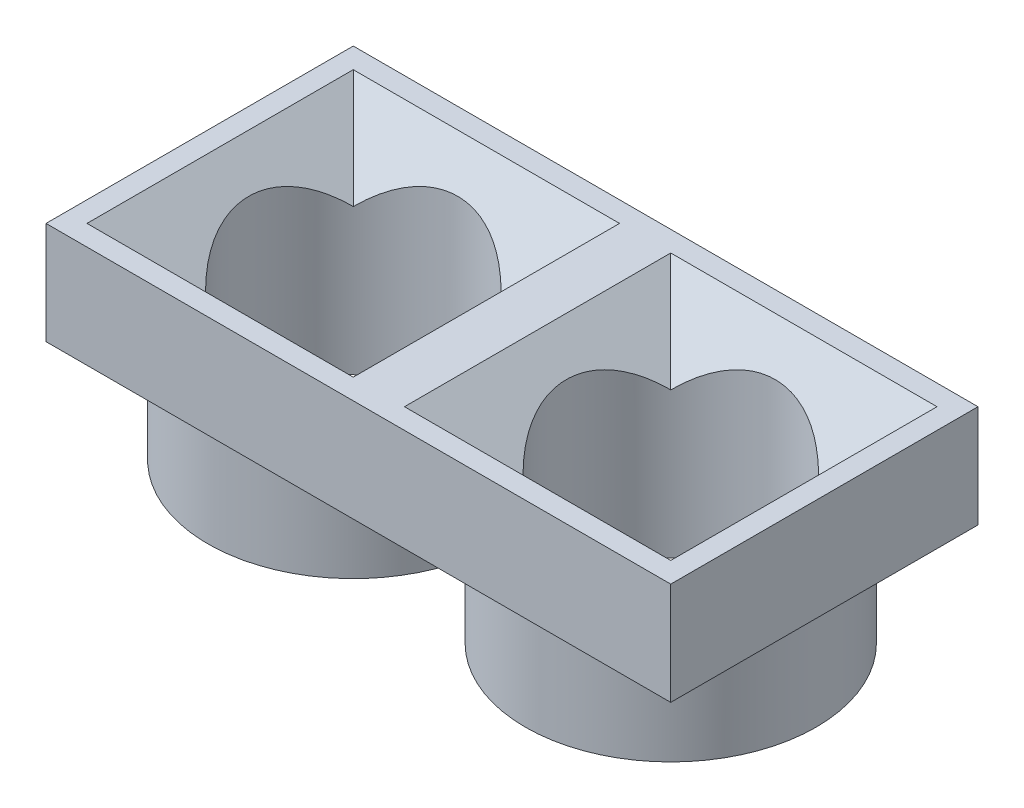
SolidWorks part; units mm, degrees
ref_plane "Front Plane" through (0, 0, 0) normal (0, 0, 1) x (1, 0, 0)
ref_plane "Top Plane" through (0, 0, 0) normal (0, 1, 0) x (1, 0, 0)
ref_plane "Right Plane" through (0, 0, 0) normal (1, 0, 0) x (0, 0, -1)
sketch "Sketch1" plane through (0, 0, 0) normal (0, 1, 0) x (1, 0, 0)
  line L1 (-15.25, 7.5) -> (15.25, 7.5)
  line L2 (-15.25, 7.5) -> (-15.25, -7.5)
  line L3 (-15.25, -7.5) -> (15.25, -7.5)
  line L4 (15.25, 7.5) -> (15.25, -7.5)
  line L5 (-15.25, 7.5) -> (15.25, -7.5) construction
  line L6 (-15.25, -7.5) -> (15.25, 7.5) construction
  point P0 (0, 0)
  dimension "D1" = 15
  dimension "D2" = 30.5
extrude "Boss-Extrude1" add sketch "Sketch1" along normal blind 5
sketch "Sketch2" plane through (0, 5, 0) normal (0, 1, 0) x (1, 0, 0)
  line L0 (15.25, 7.5) -> (-15.25, 7.5) construction
  line L1 (-14.25, 6.5) -> (-1.25, 6.5)
  line L2 (-14.25, 6.5) -> (-14.25, -6.5)
  line L3 (-14.25, -6.5) -> (-1.25, -6.5)
  line L4 (-1.25, 6.5) -> (-1.25, -6.5)
  line L5 (1.25, 6.5) -> (14.25, 6.5)
  line L6 (1.25, 6.5) -> (1.25, -6.5)
  line L7 (1.25, -6.5) -> (14.25, -6.5)
  line L8 (14.25, 6.5) -> (14.25, -6.5)
  line L9 (-15.25, -7.5) -> (15.25, -7.5) construction
  line L10 (-15.25, 7.5) -> (-15.25, -7.5) construction
  line L11 (15.25, -7.5) -> (15.25, 7.5) construction
  point P16 (0, 0)
  dimension "D1" = 1
  dimension "D2" = 1
  dimension "D3" = 1
  dimension "D4" = 1
  dimension "D5" = 1
  dimension "D6" = 1
  dimension "D7" = 28.5
  dimension "D8" = 13
  dimension "D9" = 13
extrude "Cut-Extrude1" cut sketch "Sketch2" against normal blind 3
chamfer "Chamfer1" distance 3 angle 45 8 edges at (-7.75, 2, -6.5) (-1.25, 2, 0) (-7.75, 2, 6.5) (-14.25, 2, 0) (7.75, 2, -6.5) (14.25, 2, 0) (7.75, 2, 6.5) (1.25, 2, 0)
sketch "Sketch4" plane through (0, 2, 0) normal (0, 1, 0) x (1, 0, 0)
  line L0 (-11.25, 0) -> (11.25, 0) construction
  line L1 (-11.25, 3.5) -> (-11.25, -3.5) construction
  line L2 (11.25, -3.5) -> (11.25, 3.5) construction
  line L3 (-7.75, 3.5) -> (-7.75, -3.5) construction
  line L4 (-4.25, 3.5) -> (-11.25, 3.5) construction
  line L5 (-11.25, -3.5) -> (-4.25, -3.5) construction
  line L6 (7.75, 3.5) -> (7.75, -3.5) construction
  line L7 (11.25, 3.5) -> (4.25, 3.5) construction
  line L8 (4.25, -3.5) -> (11.25, -3.5) construction
  circle A0 centre (-7.75, 0) radius 5.1
  circle A1 centre (7.75, 0) radius 5.1
  dimension "D1" = 10.2
  dimension "D2" = 10.2
extrude "Cut-Extrude3" cut sketch "Sketch4" against normal through all both and the other way through all
sketch "Sketch5" plane through (0, 0, 0) normal (0, -1, 0) x (1, 0, 0)
  circle A0 centre (-7.75, 0) radius 5.1 construction
  circle A1 centre (-7.75, 0) radius 5.1
  circle A2 centre (7.75, 0) radius 5.1 construction
  circle A3 centre (7.75, 0) radius 5.1
  circle A4 centre (-7.75, 0) radius 7.1
  circle A5 centre (7.75, 0) radius 7.1
  dimension "D1" = 2
extrude "Boss-Extrude3" add sketch "Sketch5" along normal blind 5
